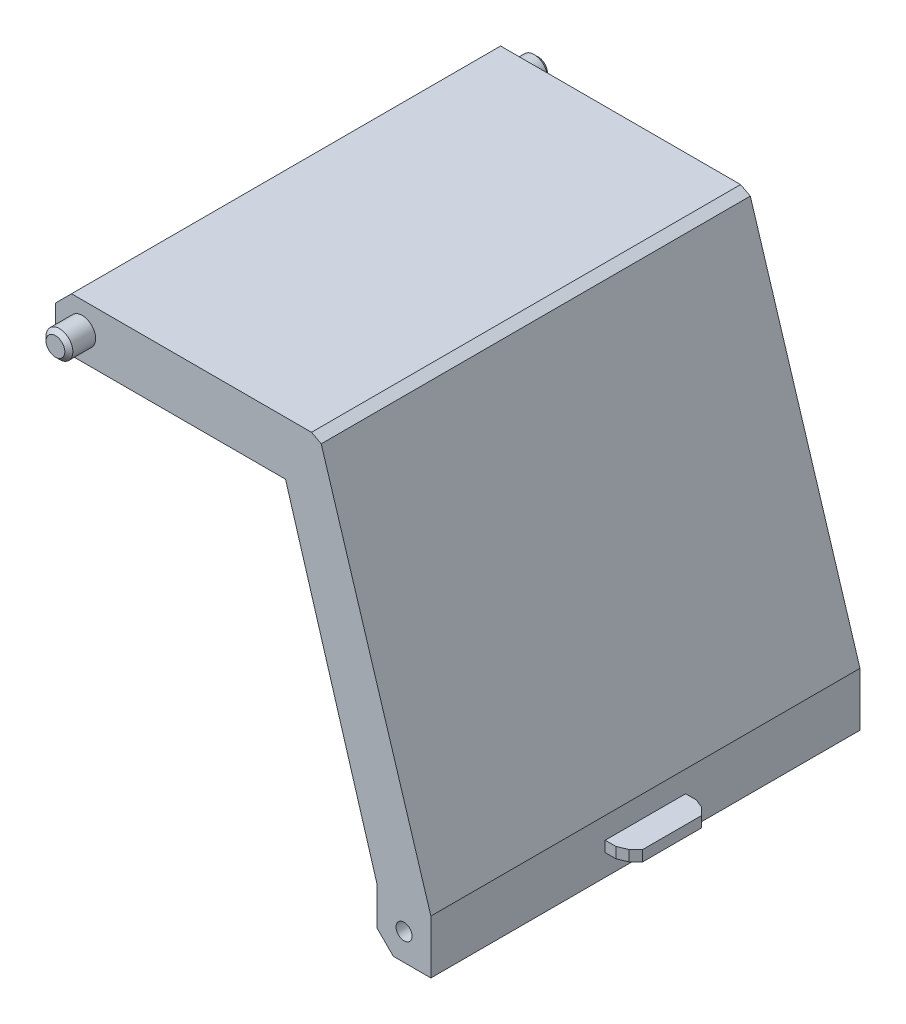
SolidWorks part; units mm, degrees
ref_plane "Front Plane" through (0, 0, 0) normal (0, 0, 1) x (1, 0, 0)
ref_plane "Top Plane" through (0, 0, 0) normal (0, 1, 0) x (1, 0, 0)
ref_plane "Right Plane" through (0, 0, 0) normal (1, 0, 0) x (0, 0, -1)
sketch "Sketch1" plane through (0, 0, 0) normal (0, 0, 1) x (1, 0, 0)
  line L0 (-5, 5) -> (-22.101, 61.9846)
  line L1 (-5, -5) -> (5, -5)
  line L2 (-5, -5) -> (-5, 5)
  line L3 (-5, 5) -> (5, 5)
  line L4 (5, -5) -> (5, 5)
  line L5 (-5, -5) -> (5, 5) construction
  line L6 (-5, 5) -> (5, -5) construction
  line L7 (5, 5) -> (-12.5931, 61.819)
  line L8 (-12.5931, 61.819) -> (-15.7407, 71.9846)
  line L13 (-15.7407, 71.9846) -> (-22.101, 71.9846)
  line L15 (-22.101, 71.9846) -> (-32.101, 71.9846)
  line L16 (-22.101, 71.9846) -> (-22.101, 61.9846)
  line L17 (-22.101, 61.9846) -> (-32.101, 61.9846)
  line L18 (-32.101, 71.9846) -> (-32.101, 61.9846)
  line L19 (-32.101, 71.9846) -> (-65.001, 71.9846)
  line L20 (-32.101, 71.9846) -> (-32.101, 61.9846)
  line L21 (-32.101, 61.9846) -> (-65.001, 61.9846)
  line L22 (-65.001, 71.9846) -> (-65.001, 61.9846)
  point P0 (0, 0)
  dimension "D1" = 10
  dimension "D2" = 10
  dimension "D3" = 10
  dimension "D4" = 32.9
extrude "Boss-Extrude1" add sketch "Sketch1" along normal blind 80 contours L15 | L8 L13 L3 L7 | L1 L4 L3 L2 | L19 L22 L21 L18 region at (0, 0, 0) region at (-9.7904, 37.4009, 0) region at (-27.101, 66.9846, 0) region at (-48.551, 66.9846, 0)
chamfer "Chamfer1" distance 3 angle 45 1 edges at (-5, -5, 40)
sketch "Sketch2" plane through (0, 0, 80) normal (0, 0, 1) x (1, 0, 0)
  line L0 (-65.001, 66.9846) -> (-60.001, 66.9846)
  line L1 (-65.001, 71.9846) -> (-65.001, 61.9846) construction
  circle A1 centre (-60.001, 66.9846) radius 2.5
extrude "Boss-Extrude2" add sketch "Sketch2" along normal blind 5 from surface contours A1 starting at face at (-18.8715, 29.5487, 80)
extrude "Boss-Extrude3" add sketch "Sketch2<2>" against normal blind 5 from surface contours A1 starting at face at (-18.8715, 29.5487, 0)
sketch "Sketch2<2>" plane through (0, 0, 80) normal (0, 0, 1) x (1, 0, 0) same geometry as "Sketch2"
chamfer "Chamfer3" distance 0.75 angle 45 2 edges at (-57.501, 66.9846, -5) (-57.501, 66.9846, 85)
sketch "Sketch3" plane through (5, 0, 0) normal (1, 0, 0) x (0, 0, -1)
  line L0 (-40, -5) -> (-40, 0)
  line L1 (-80, -5) -> (0, -5) construction
  line L3 (-47.5, -1) -> (-32.5, -1)
  line L4 (-47.5, -1) -> (-47.5, 1)
  line L5 (-47.5, 1) -> (-32.5, 1)
  line L6 (-32.5, -1) -> (-32.5, 1)
  line L7 (-47.5, -1) -> (-32.5, 1) construction
  line L8 (-47.5, 1) -> (-32.5, -1) construction
  dimension "D1" = 15
  dimension "D2" = 2
extrude "Boss-Extrude4" add sketch "Sketch3" along normal blind 5 contours L5 L6 L3 L4
chamfer "Chamfer4" distance 2 angle 45 2 edges at (10, 0, 32.5) (10, 0, 47.5)
chamfer "Chamfer5" distance 1 angle 22.5 2 edges at (8, 0, 32.5) (8, 0, 47.5) first distance on face at (9, 0, 33.5) first distance on face at (9, 0, 46.5)
chamfer "Chamfer6" distance 3 angle 45 2 edges at (-65.001, 71.9846, 40) (-65.001, 61.9846, 40)
sketch "Sketch4" plane through (0, 0, 80) normal (0, 0, 1) x (1, 0, 0)
  line L1 (5, -5) -> (0, -5)
  line L2 (5, -5) -> (5, 0)
  line L3 (5, 0) -> (0, 0)
  line L4 (0, -5) -> (0, 0)
  circle A0 centre (0, 0) radius 1.5
extrude "Cut-Extrude1" cut sketch "Sketch4" against normal blind 5 contours A0
extrude "Cut-Extrude2" cut sketch "Sketch4<3>" along normal blind 5 from surface contours A0 starting at face at (-57.501, 66.9846, 0)
sketch "Sketch4<3>" plane through (0, 0, 80) normal (0, 0, 1) x (1, 0, 0) same geometry as "Sketch4"
chamfer "Chamfer8" distance 1 angle 45 1 edges at (-15.7407, 71.9846, 40) first distance on face at (-5.3704, 38.4923, 40)
